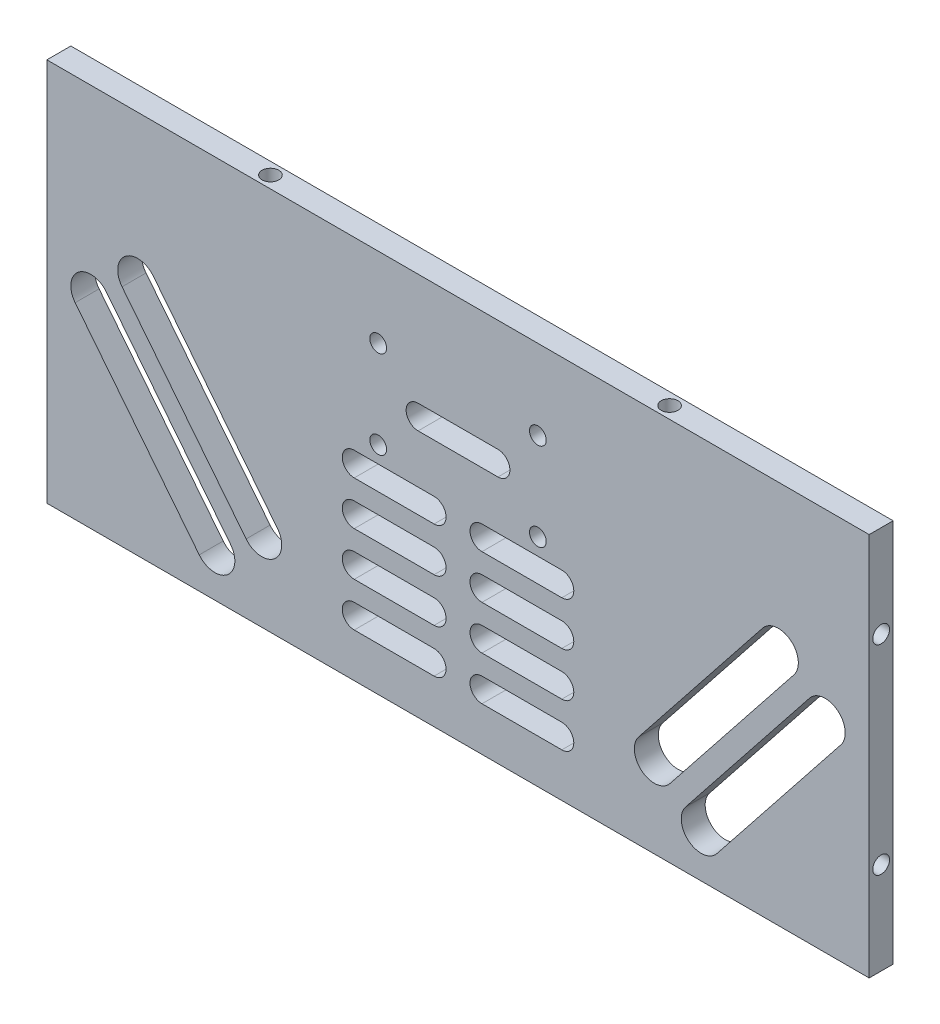
SolidWorks part; units mm, degrees
ref_plane "Front Plane" through (0, 0, 0) normal (1, 0, 0) x (0, 1, 0)
ref_plane "Top Plane" through (0, 0, 0) normal (0, 0, 1) x (0, 1, 0)
ref_plane "Right Plane" through (0, 0, 0) normal (0, 1, 0) x (-1, 0, 0)
sketch "Sketch1" plane through (0, 0, 0) normal (0, 0, 1) x (0, 1, 0)
  line L0 (11, 163.9146) -> (50.1625, 195) construction
  line L1 (0, 0) -> (96.2019, 0)
  line L2 (0, 0) -> (0, 206)
  line L3 (0, 206) -> (96.2019, 206)
  line L4 (96.2019, 0) -> (96.2019, 206)
  line L5 (7.8915, 167.8308) -> (47.0539, 198.9162)
  line L6 (14.1085, 159.9983) -> (53.271, 191.0838)
  line L7 (20.3256, 152.1659) -> (59.4881, 183.2513) construction
  line L8 (17.2171, 156.0821) -> (56.3795, 187.1675)
  line L9 (23.4342, 148.2496) -> (62.5966, 179.335)
  line L10 (20.3256, 53.8341) -> (59.4881, 22.7487) construction
  line L11 (23.4342, 57.7504) -> (62.5966, 26.665)
  line L12 (17.2171, 49.9179) -> (56.3795, 18.8325)
  line L13 (11, 42.0854) -> (50.1625, 11) construction
  line L14 (14.1085, 46.0017) -> (53.271, 14.9162)
  line L15 (7.8915, 38.1692) -> (47.0539, 7.0838)
  line L16 (6, 200) -> (90.2019, 200) construction
  line L17 (90.2019, 6) -> (90.2019, 200) construction
  line L18 (6, 6) -> (90.2019, 6) construction
  line L19 (6, 6) -> (6, 200) construction
  line L20 (55.8833, 147.5809) -> (78.9144, 118.5655) construction
  line L21 (65.5213, 70.5614) -> (46.6427, 46.7775) construction
  line L22 (96.2019, 103) -> (0, 103) construction
  line L23 (14, 129) -> (14, 109) construction
  line L24 (17, 129) -> (17, 109)
  line L25 (11, 129) -> (11, 109)
  line L26 (25, 129) -> (25, 109) construction
  line L27 (28, 129) -> (28, 109)
  line L28 (22, 129) -> (22, 109)
  line L29 (36, 129) -> (36, 109) construction
  line L30 (39, 129) -> (39, 109)
  line L31 (33, 129) -> (33, 109)
  line L32 (47, 129) -> (47, 109) construction
  line L33 (50, 129) -> (50, 109)
  line L34 (44, 129) -> (44, 109)
  line L41 (14, 77) -> (14, 97) construction
  line L42 (17, 77) -> (17, 97)
  line L43 (11, 77) -> (11, 97)
  line L44 (25, 77) -> (25, 97) construction
  line L45 (28, 77) -> (28, 97)
  line L46 (22, 77) -> (22, 97)
  line L47 (36, 77) -> (36, 97) construction
  line L48 (39, 77) -> (39, 97)
  line L49 (33, 77) -> (33, 97)
  line L50 (47, 77) -> (47, 97) construction
  line L51 (50, 77) -> (50, 97)
  line L52 (44, 77) -> (44, 97)
  line L53 (54.2019, 83) -> (76.2019, 83) construction
  line L56 (54.2019, 83) -> (54.2019, 123) construction
  line L59 (65.2019, 113) -> (65.2019, 93) construction
  line L60 (68.2019, 113) -> (68.2019, 93)
  line L61 (62.2019, 113) -> (62.2019, 93)
  line L67 (54.2019, 123) -> (76.2019, 123) construction
  line L68 (76.2019, 83) -> (76.2019, 123) construction
  line L69 (54.2019, 83) -> (76.2019, 123) construction
  line L70 (54.2019, 123) -> (76.2019, 83) construction
  line L95 (69, 129) -> (69, 109) construction
  line L96 (72, 129) -> (72, 109)
  line L97 (66, 129) -> (66, 109)
  line L98 (58, 129) -> (58, 109) construction
  line L99 (61, 129) -> (61, 109)
  line L100 (55, 129) -> (55, 109)
  line L101 (69, 129) -> (69, 109) construction
  line L102 (72, 129) -> (72, 109)
  line L103 (66, 129) -> (66, 109)
  line L104 (58, 129) -> (58, 109) construction
  line L105 (61, 129) -> (61, 109)
  line L106 (55, 129) -> (55, 109)
  arc A0 (7.8915, 167.8308) -> (14.1085, 159.9983) centre (11, 163.9146) ccw
  arc A1 (53.271, 191.0838) -> (47.0539, 198.9162) centre (50.1625, 195) ccw
  arc A2 (17.2171, 156.0821) -> (23.4342, 148.2496) centre (20.3256, 152.1659) ccw
  arc A3 (62.5966, 179.335) -> (56.3795, 187.1675) centre (59.4881, 183.2513) ccw
  arc A4 (23.4342, 57.7504) -> (17.2171, 49.9179) centre (20.3256, 53.8341) ccw
  arc A5 (56.3795, 18.8325) -> (62.5966, 26.665) centre (59.4881, 22.7487) ccw
  arc A6 (14.1085, 46.0017) -> (7.8915, 38.1692) centre (11, 42.0854) ccw
  arc A7 (47.0539, 7.0838) -> (53.271, 14.9162) centre (50.1625, 11) ccw
  circle A9 centre (76.2019, 123) radius 2.1
  circle A11 centre (76.2019, 83) radius 2.1
  arc A12 (17, 129) -> (11, 129) centre (14, 129) ccw
  arc A13 (11, 109) -> (17, 109) centre (14, 109) ccw
  arc A14 (28, 129) -> (22, 129) centre (25, 129) ccw
  arc A15 (22, 109) -> (28, 109) centre (25, 109) ccw
  arc A16 (39, 129) -> (33, 129) centre (36, 129) ccw
  arc A17 (33, 109) -> (39, 109) centre (36, 109) ccw
  arc A18 (50, 129) -> (44, 129) centre (47, 129) ccw
  arc A19 (44, 109) -> (50, 109) centre (47, 109) ccw
  arc A24 (17, 77) -> (11, 77) centre (14, 77) cw
  arc A25 (11, 97) -> (17, 97) centre (14, 97) cw
  arc A26 (28, 77) -> (22, 77) centre (25, 77) cw
  arc A27 (22, 97) -> (28, 97) centre (25, 97) cw
  arc A28 (39, 77) -> (33, 77) centre (36, 77) cw
  arc A29 (33, 97) -> (39, 97) centre (36, 97) cw
  arc A30 (50, 77) -> (44, 77) centre (47, 77) cw
  arc A31 (44, 97) -> (50, 97) centre (47, 97) cw
  arc A36 (68.2019, 113) -> (62.2019, 113) centre (65.2019, 113) ccw
  arc A37 (62.2019, 93) -> (68.2019, 93) centre (65.2019, 93) ccw
  circle A42 centre (54.2019, 123) radius 2.1
  circle A43 centre (54.2019, 83) radius 2.1
  arc A64 (72, 129) -> (66, 129) centre (69, 129) ccw
  arc A65 (66, 109) -> (72, 109) centre (69, 109) ccw
  arc A66 (61, 129) -> (55, 129) centre (58, 129) ccw
  arc A67 (55, 109) -> (61, 109) centre (58, 109) ccw
  point P7 (30.5812, 179.4573)
  point P12 (39.9068, 167.7086)
  point P19 (39.9068, 38.2914)
  point P26 (30.5812, 26.5427)
  point P40 (65.2019, 103)
  point P42 (65.2019, 103)
  point P54 (14, 119)
  point P59 (65.2019, 103)
  point P63 (25, 119)
  point P70 (36, 119)
  point P77 (47, 119)
  point P84 (69, 119)
  point P94 (91.2696, 103)
  point P97 (14, 87)
  point P104 (25, 87)
  point P111 (36, 87)
  point P118 (47, 87)
  point P146 (58, 119)
  point P153 (69, 119)
  point P160 (58, 119)
  point P167 (69, 119)
  point P174 (58, 119)
  point P181 (69, 119)
  point P188 (58, 119)
  point P195 (69, 119)
  point P202 (58, 119)
  point P209 (69, 119)
  point P216 (58, 119)
  point P223 (69, 119)
  point P230 (58, 119)
  dimension "D9" = 4.2
  dimension "D1" = 96.2019
  dimension "D2" = 206
  dimension "D4" = 5
  dimension "D5" = 5
  dimension "D6" = 103.118
  dimension "D7" = 10
  dimension "D8" = 50
  dimension "D10" = 20
  dimension "D11" = 20
  dimension "D14" = 5
  dimension "D15" = 5
  dimension "D16" = 6
  dimension "20" = 20
  dimension "D17" = 6
  dimension "D18" = 20
  dimension "D19" = 6
  dimension "D12" = 22
  dimension "D3" = 6
  dimension "D13" = 6
extrude "Boss-Extrude1" add sketch "Sketch1" along normal blind 6
sketch "Sketch2" plane through (0, 0, 0) normal (0, -1, 0) x (1, 0, 0)
  line L2 (-206, 3) -> (0, 3) construction
  line L3 (-206, 6) -> (-206, 0) construction
  line L4 (0, 6) -> (0, 0) construction
  line L5 (-103, 6) -> (-103, 0) construction
  line L6 (-206, 6) -> (0, 6) construction
  line L7 (-206, 0) -> (0, 0) construction
  circle A0 centre (-153, 3) radius 2.1
  circle A1 centre (-53, 3) radius 2.1
  dimension "D1" = 4.2
  dimension "D2" = 50
extrude "Cut-Extrude1" cut sketch "Sketch2" against normal blind 14
extrude "Cut-Extrude2" cut sketch "Sketch2<2>" along normal blind 14 from surface starting at face at (-103, 96.2019, 3)
sketch "Sketch2<2>" plane through (0, 0, 0) normal (0, -1, 0) x (1, 0, 0) same geometry as "Sketch2"
sketch "Sketch3" plane through (0, 0, 0) normal (1, 0, 0) x (0, 1, 0)
  line L0 (82.2019, 3) -> (96.2019, 3) construction
  line L1 (0, 3) -> (96.2019, 3) construction
  line L2 (0, 6) -> (0, 0) construction
  line L3 (96.2019, 6) -> (96.2019, 0) construction
  line L4 (0, 6) -> (96.2019, 6) construction
  line L5 (48.1009, 6) -> (48.1009, 0) construction
  line L6 (0, 0) -> (96.2019, 0) construction
  circle A0 centre (23.1009, 3) radius 2.1
  circle A1 centre (73.1009, 3) radius 2.1
  dimension "D1" = 4.2
  dimension "D2" = 50
extrude "Cut-Extrude3" cut sketch "Sketch3" against normal blind 14
extrude "Cut-Extrude4" cut sketch "Sketch3<2>" along normal blind 14 from surface starting at face at (-206, 48.1009, 3)
sketch "Sketch3<2>" plane through (0, 0, 0) normal (1, 0, 0) x (0, 1, 0) same geometry as "Sketch3"
equation "\"MotorDriverLength\"= 60mm"
equation "\"MotorLength\"= 60"
equation "\"MotorDriverWidth\"=44"
equation "\"MotorWidth\"= 37"
equation "\"InnerWallThickness\"=3"
equation "\"BatteryWidth\"= 60"
equation "\"OuterWallThickness\" = 6"
equation "\"CompartmentHeight\"=37"
equation "\"CompartmentWidth\"= \"MotorDriverLength\""
equation "\"MotorDiameter\"=37"
equation "\"BatteryHeight\"=24.2019"
equation "\"MotorDriverHeight\"=28"
equation "\"CircuitHeight\"=30"
equation "\"FanThickness\"= 10"
equation "\"FanHeight\"=50"
equation "\"MotorShaftHole\"=12"
equation "\"BearingBore\"=4"
equation "\"MinShinWidth\"= 20"
equation "\"ShinThickness\"=10"
equation "\"PivotDistance\"=30"
equation "\"ThighLength\"= 200"
equation "\"KneeLength\" =20"
equation "\"HipBore\"=27"
equation "\"ThighThickness\"=20"
equation "\"MaxBending\"=135"
equation "\"MaxStretchingAngle\"= 140"
equation "\"ThighJointDistance\"=157.485"
equation "\"ShinLength\"=120"
equation "\"BearingDiameter\"= 10"
equation "\"CircuitLength\"=50"
equation "\"ChessisInnerWidth\"= \"OuterWallThickness\" * 2 + \"MotorDriverLength\" + \"MotorDiameter\" + \"InnerWallThickness\" * 3 + \"CircuitLength\""
equation "\"ChessisHeight\"= \"BatteryHeight\" + 10 + \"InnerWallThickness\" + \"MotorDiameter\" + 10 + \"OuterWallThickness\" * 2"
equation "\"D1@Sketch1\"=\"ChessisHeight\""
equation "\"ChassisWidth\"= \"MotorDriverWidth\"*4+30"
equation "\"D2@Sketch1\"=\"ChassisWidth\""
equation "\"D1@Boss-Extrude1\"=\"OuterWallThickness\""
